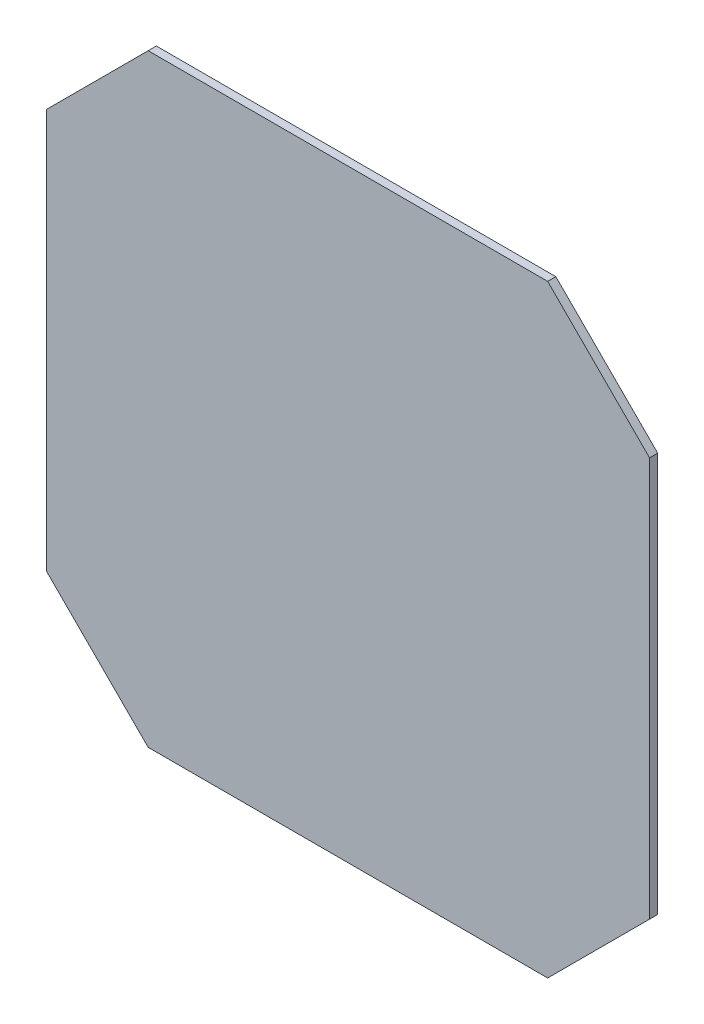
SolidWorks part; units mm, degrees
ref_plane "Front Plane" through (0, 0, 0) normal (0, 0, 1) x (1, 0, 0)
ref_plane "Top Plane" through (0, 0, 0) normal (0, 1, 0) x (1, 0, 0)
ref_plane "Right Plane" through (0, 0, 0) normal (1, 0, 0) x (0, 0, -1)
sketch "Sketch1" plane through (0, 0, 0) normal (0, 0, 1) x (1, 0, 0)
  line L0 (-74, 49) -> (-49, 74)
  line L1 (-49, -74) -> (49, -74)
  line L2 (-74, -49) -> (-74, 49)
  line L3 (-49, 74) -> (49, 74)
  line L4 (74, -49) -> (74, 49)
  line L5 (-74, -74) -> (74, 74) construction
  line L6 (-74, 74) -> (74, -74) construction
  line L7 (49, 74) -> (74, 49)
  line L8 (49, -74) -> (74, -49)
  line L9 (-74, -49) -> (-49, -74)
  point P0 (0, 0)
  dimension "D1" = 148
extrude "Boss-Extrude1" add sketch "Sketch1" along normal blind 2
ref_axis "Axis1" through (0, 0, -0.1) along (0, 0, 1)
ref_plane "Plane1" through (0, 0, 0) normal (-0.7071, 0.7071, 0) x (0, 0, 1)
ref_plane "Plane2" through (0, 0, 0) normal (0.7071, 0.7071, 0) x (0, 0, 1)
